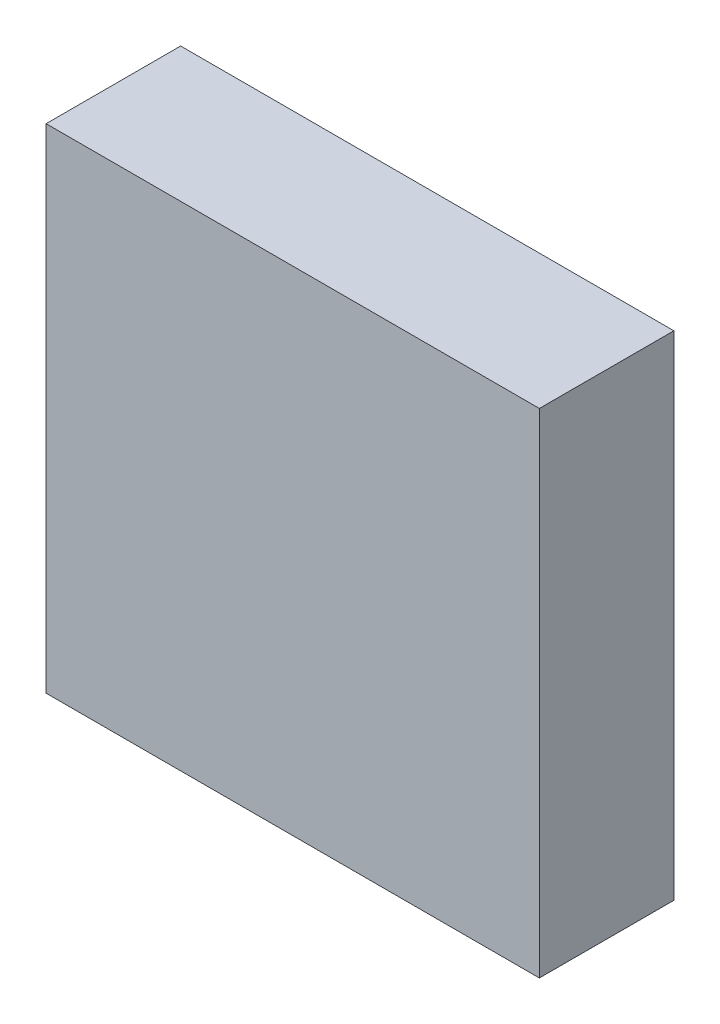
SolidWorks part; units mm, degrees
ref_plane "Front Plane" through (0, 0, 0) normal (0, 0, 1) x (1, 0, 0)
ref_plane "Top Plane" through (0, 0, 0) normal (0, 1, 0) x (1, 0, 0)
ref_plane "Right Plane" through (0, 0, 0) normal (1, 0, 0) x (0, 0, -1)
sketch "Sketch1" plane through (0, 0, 0) normal (0, 0, 1) x (1, 0, 0)
  line L1 (0, 0) -> (220, 0)
  line L2 (0, 0) -> (0, 220)
  line L3 (0, 220) -> (220, 220)
  line L4 (220, 0) -> (220, 220)
extrude "Boss-Extrude1" add sketch "Sketch1" along normal blind 60
